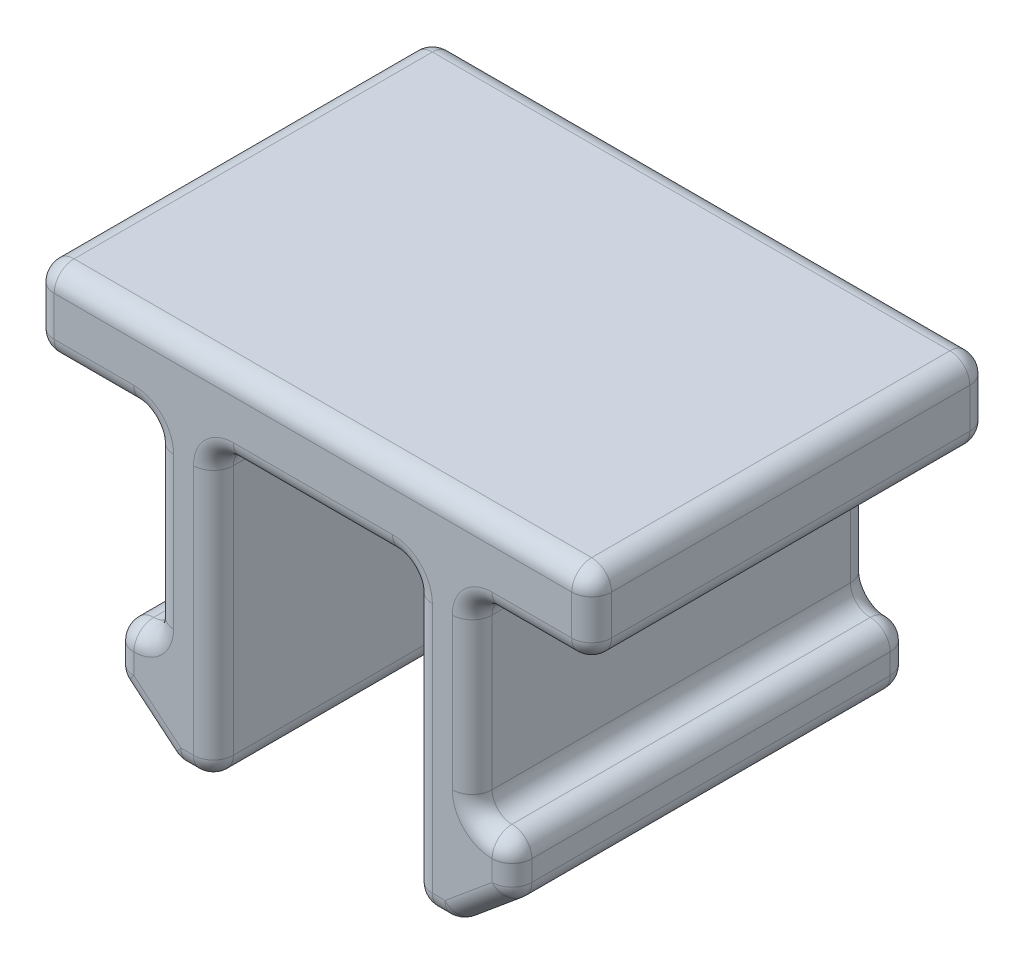
SolidWorks part; units mm, degrees
ref_plane "前视基准面" through (0, 0, 0) normal (0, 0, 1) x (1, 0, 0)
ref_plane "上视基准面" through (0, 0, 0) normal (0, 1, 0) x (1, 0, 0)
ref_plane "右视基准面" through (0, 0, 0) normal (1, 0, 0) x (0, 0, -1)
sketch "草图1" plane through (0, 0, 0) normal (0, 0, 1) x (1, 0, 0)
  line L0 (28.7983, 30.5077) -> (42.7983, 30.5077)
  line L1 (28.7983, 30.5077) -> (28.7983, 28.5077)
  line L2 (28.7983, 28.5077) -> (31.7983, 28.5077)
  line L3 (42.7983, 28.5077) -> (42.7983, 30.5077)
  line L4 (39.7983, 28.5077) -> (42.7983, 28.5077)
  line L5 (31.7983, 28.5077) -> (31.7983, 23.7077)
  line L6 (31.7983, 23.7077) -> (30.7983, 23.7077)
  line L7 (30.7983, 23.7077) -> (30.7983, 22.4577)
  line L9 (32.2983, 21.2077) -> (33.2983, 21.2077)
  line L10 (33.2983, 21.2077) -> (33.2983, 28.5077)
  line L11 (33.2983, 28.5077) -> (38.2983, 28.5077)
  line L12 (38.2983, 21.2077) -> (38.2983, 28.5077)
  line L13 (39.2983, 21.2077) -> (38.2983, 21.2077)
  line L15 (40.7983, 23.7077) -> (40.7983, 22.4577)
  line L16 (39.7983, 23.7077) -> (40.7983, 23.7077)
  line L17 (39.7983, 28.5077) -> (39.7983, 23.7077)
  line L18 (30.7983, 22.4577) -> (32.2983, 21.2077)
  line L19 (39.2983, 21.2077) -> (40.7983, 22.4577)
extrude "凸台-拉伸1" add sketch "草图1" along normal blind 10
fillet "圆角1" radius 0.5 50 edges at (40.7983, 22.4577, 5) (33.2983, 28.5077, 5) (38.2983, 28.5077, 5) (38.2983, 21.2077, 5) (39.2983, 21.2077, 5) (40.7983, 23.7077, 5) (39.7983, 23.7077, 5) (39.7983, 28.5077, 5) (42.7983, 28.5077, 5) (42.7983, 30.5077, 5) (28.7983, 30.5077, 5) (28.7983, 28.5077, 5) (31.7983, 28.5077, 5) (31.7983, 23.7077, 5) (30.7983, 23.7077, 5) (30.7983, 22.4577, 5) (32.2983, 21.2077, 5) (33.2983, 21.2077, 5) (35.7983, 30.5077, 10) (42.7983, 29.5077, 10) (41.2983, 28.5077, 10) (39.7983, 26.1077, 10) (40.7983, 23.0827, 10) (40.0483, 21.8327, 10) (38.7983, 21.2077, 10) (38.2983, 24.8577, 10) (35.7983, 28.5077, 10) (33.2983, 24.8577, 10) (32.7983, 21.2077, 10) (31.5483, 21.8327, 10) (30.7983, 23.0827, 10) (31.7983, 26.1077, 10) (30.2983, 28.5077, 10) (28.7983, 29.5077, 10) (30.2983, 28.5077, 0) (31.7983, 26.1077, 0) (30.7983, 23.0827, 0) (31.5483, 21.8327, 0) (32.7983, 21.2077, 0) (33.2983, 24.8577, 0) (35.7983, 28.5077, 0) (38.2983, 24.8577, 0) (38.7983, 21.2077, 0) (40.0483, 21.8327, 0) (40.7983, 23.0827, 0) (39.7983, 26.1077, 0) (41.2983, 28.5077, 0) (42.7983, 29.5077, 0) (35.7983, 30.5077, 0) (28.7983, 29.5077, 0)
